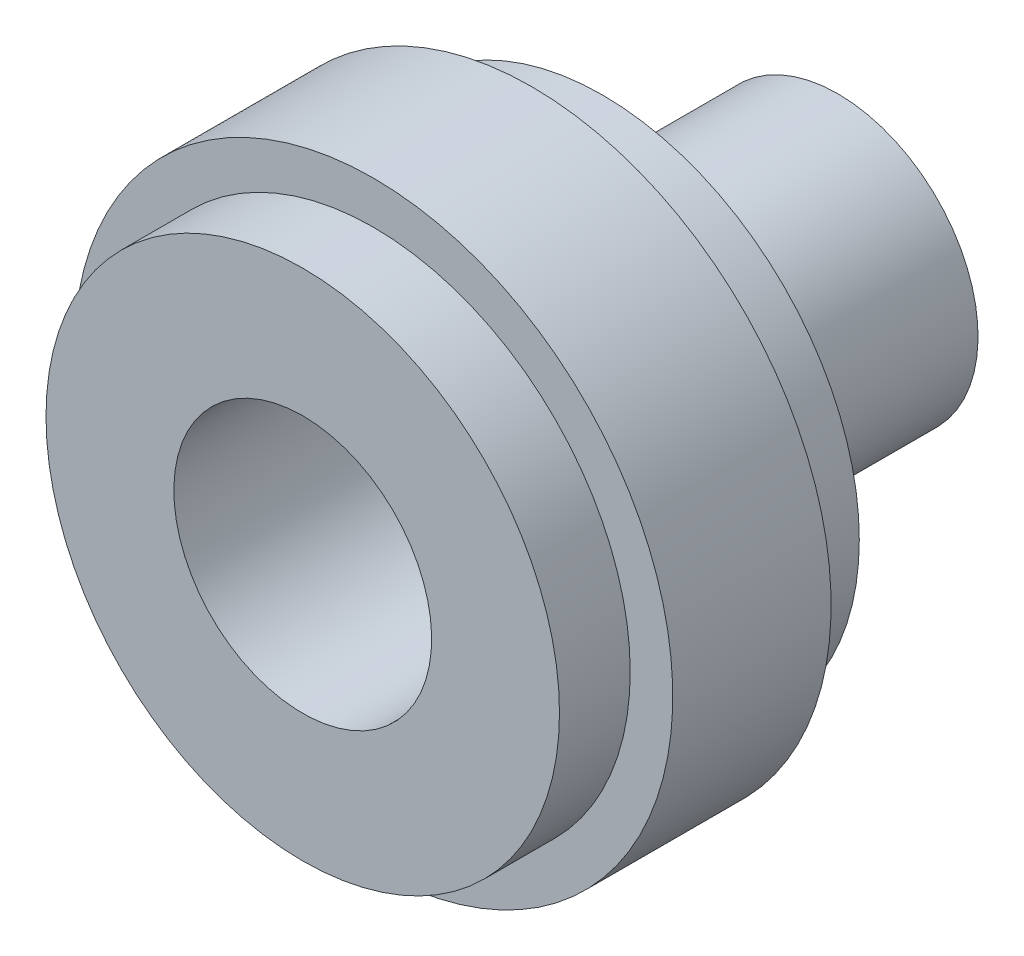
SolidWorks part; units mm, degrees
material "Custom Plastic"
ref_plane "Front Plane" through (0, 0, 0) normal (0, 0, 1) x (1, 0, 0)
ref_plane "Top Plane" through (0, 0, 0) normal (0, 1, 0) x (1, 0, 0)
ref_plane "Right Plane" through (0, 0, 0) normal (1, 0, 0) x (0, 0, -1)
sketch "Sketch2" plane through (0, 0, 0) normal (1, 0, 0) x (0, 0, -1)
  line L0 (0, 0) -> (-6.9967, 0) construction
  line L1 (0, 0) -> (0, 9.8665) construction
  line L2 (-5.4356, 4.6736) -> (1.1938, 4.6736)
  line L3 (1.1938, 4.6736) -> (1.1938, 1.7526)
  line L4 (1.1938, 1.7526) -> (13.97, 1.7526)
  line L5 (13.97, 1.7526) -> (13.97, 5.08)
  line L6 (13.97, 5.08) -> (5.4356, 5.08)
  line L7 (5.4356, 5.08) -> (5.4356, 9.3091)
  line L8 (5.4356, 9.3091) -> (2.8702, 9.3091)
  line L9 (2.8702, 9.3091) -> (2.8702, 10.8521)
  line L10 (2.8702, 10.8521) -> (-2.8702, 10.8521)
  line L11 (-2.8702, 10.8521) -> (-2.8702, 9.3091)
  line L12 (-2.8702, 9.3091) -> (-5.4356, 9.3091)
  line L13 (-5.4356, 9.3091) -> (-5.4356, 4.6736)
  dimension "D1" = 9.3472
  dimension "D2" = 3.5052
  dimension "D3" = 6.6294
  dimension "D4" = 18.6182
  dimension "D5" = 5.7404
  dimension "D6" = 10.8712
  dimension "D7" = 21.7043
  dimension "D8" = 10.16
  dimension "D9" = 19.4056
revolve "Revolve1" add sketch "Sketch2" angle 360 about L0
